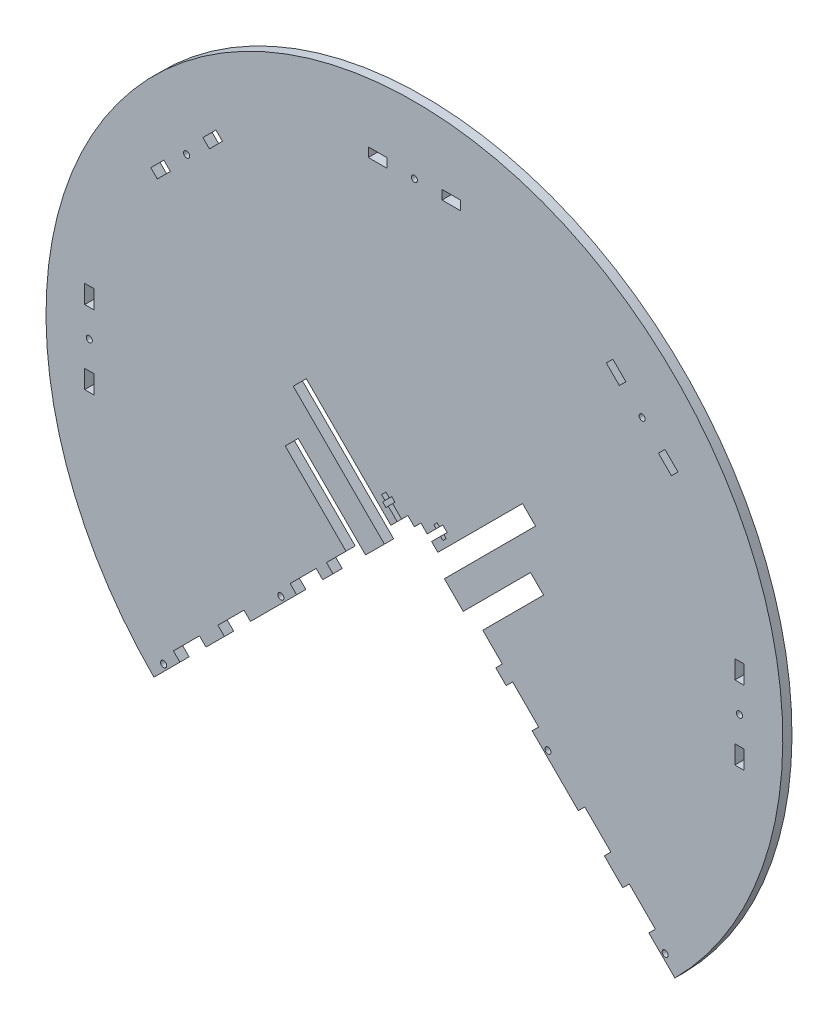
SolidWorks part; units mm, degrees
ref_plane "Front Plane" through (0, 0, 0) normal (0, 0, 1) x (1, 0, 0)
ref_plane "Top Plane" through (0, 0, 0) normal (0, 1, 0) x (1, 0, 0)
ref_plane "Right Plane" through (0, 0, 0) normal (1, 0, 0) x (0, 0, -1)
sketch "Sketch1" plane through (0, 0, 0) normal (0, 0, 1) x (1, 0, 0)
  circle A0 centre (0, -210.9923) radius 254
  arc A1 (184.0391, -386.0511) -> (248.1989, -264.9673) centre (0, -210.9923) ccw construction
extrude "Boss-Extrude1" add sketch "Sketch1" along normal blind 6.35 contours A0
sketch "Sketch3" plane through (0, 0, 0) normal (0, 0, -1) x (-1, 0, 0)
  line L0 (179.6051, -390.5974) -> (0, -210.9923)
  line L1 (0, -210.9923) -> (-179.6051, -390.5974)
  line L2 (91.3112, -302.3035) -> (113.0075, -323.9998) construction
  line L3 (-179.6051, -390.5974) -> (-172.1335, -383.1258) construction
  circle A0 centre (0, -210.9923) radius 254 construction
  arc A1 (179.6051, -390.5974) -> (-179.6051, -390.5974) centre (0, -210.9923) cw
extrude "Cut-Extrude1" cut sketch "Sketch3" against normal through all
sketch "Sketch4" plane through (0, 0, 6.35) normal (0, 0, 1) x (1, 0, 0)
  line L0 (-161.6446, -372.6369) -> (-166.1347, -368.1468)
  line L1 (-161.6446, -372.6369) -> (-143.6841, -354.6764)
  line L2 (-166.1347, -368.1468) -> (-148.1742, -350.1862)
  line L3 (-143.6841, -354.6764) -> (-148.1742, -350.1862)
  line L4 (-179.6051, -390.5974) -> (0, -210.9923) construction
  line L5 (-166.1347, -368.1468) -> (-161.6446, -372.6369) construction
  line L7 (-130.9681, -341.9603) -> (-135.4582, -337.4702)
  line L8 (-130.9681, -341.9603) -> (-113.0075, -323.9998)
  line L9 (-135.4582, -337.4702) -> (-117.4977, -319.5097)
  line L10 (-113.0075, -323.9998) -> (-117.4977, -319.5097)
  line L11 (-81.1905, -292.1828) -> (-85.6806, -287.6926)
  line L12 (-81.1905, -292.1828) -> (-63.23, -274.2223)
  line L13 (-85.6806, -287.6926) -> (-67.7201, -269.7321)
  line L14 (-63.23, -274.2223) -> (-67.7201, -269.7321)
  line L15 (-85.6806, -287.6926) -> (-81.1905, -292.1828) construction
  line L17 (-56.1266, -267.1189) -> (-60.6167, -262.6287)
  line L18 (-56.1266, -267.1189) -> (-33.676, -244.6682)
  line L19 (-60.6167, -262.6287) -> (-38.1661, -240.1781)
  line L20 (-33.676, -244.6682) -> (-38.1661, -240.1781)
  line L21 (-11.6893, -222.6816) -> (-16.1795, -218.1915)
  line L22 (-11.6893, -222.6816) -> (0, -210.9923)
  line L23 (-16.1795, -218.1915) -> (-4.4901, -206.5021)
  line L24 (0, -210.9923) -> (-4.4901, -206.5021)
  line L25 (-16.1795, -218.1915) -> (-11.6893, -222.6816) construction
  line L27 (-143.6841, -354.6764) -> (-148.1742, -350.1862) construction
  line L28 (-135.4582, -337.4702) -> (-130.9681, -341.9603) construction
  line L29 (-113.0075, -323.9998) -> (-117.4977, -319.5097) construction
  line L30 (-63.23, -274.2223) -> (-67.7201, -269.7321) construction
  line L31 (0, -210.9923) -> (-4.4901, -206.5021) construction
  line L32 (-60.6167, -262.6287) -> (-38.1661, -240.1781) construction
  line L33 (-60.6167, -262.6287) -> (-56.1266, -267.1189) construction
  line L34 (-38.1661, -240.1781) -> (-33.676, -244.6682) construction
extrude "Cut-Extrude2" cut sketch "Sketch4" against normal through all
mirror "Mirror1" about plane through (0, 0, 0) normal (1, 0, 0) of "Cut-Extrude2"
sketch "Sketch5" plane through (0, 0, 6.35) normal (0, 0, 1) x (1, 0, 0)
  line L0 (177.245, -91.8888) -> (181.7351, -87.3987)
  line L1 (-31.75, 0) -> (-19.05, 0)
  line L2 (-31.75, 0) -> (-31.75, -6.35)
  line L3 (-31.75, -6.35) -> (-19.05, -6.35)
  line L4 (-19.05, 0) -> (-19.05, -6.35)
  line L5 (19.05, 0) -> (31.75, 0)
  line L6 (19.05, 0) -> (19.05, -6.35)
  line L7 (19.05, -6.35) -> (31.75, -6.35)
  line L8 (31.75, 0) -> (31.75, -6.35)
  line L9 (-227.33, -242.7423) -> (-220.98, -242.7423)
  line L10 (-227.33, -242.7423) -> (-227.33, -230.0423)
  line L11 (-227.33, -230.0423) -> (-220.98, -230.0423)
  line L12 (-220.98, -242.7423) -> (-220.98, -230.0423)
  line L13 (-227.33, -179.2423) -> (-220.98, -179.2423)
  line L14 (-227.33, -179.2423) -> (-227.33, -191.9423)
  line L15 (-227.33, -191.9423) -> (-220.98, -191.9423)
  line L16 (-220.98, -179.2423) -> (-220.98, -191.9423)
  line L17 (220.98, -179.2423) -> (227.33, -179.2423)
  line L18 (220.98, -179.2423) -> (220.98, -191.9423)
  line L19 (220.98, -191.9423) -> (227.33, -191.9423)
  line L20 (227.33, -179.2423) -> (227.33, -191.9423)
  line L21 (220.98, -230.0423) -> (227.33, -230.0423)
  line L22 (220.98, -230.0423) -> (220.98, -242.7423)
  line L23 (220.98, -242.7423) -> (227.33, -242.7423)
  line L24 (227.33, -230.0423) -> (227.33, -242.7423)
  line L25 (177.245, -91.8888) -> (168.2647, -82.9085)
  line L26 (181.7351, -87.3987) -> (172.7548, -78.4184)
  line L27 (168.2647, -82.9085) -> (172.7548, -78.4184)
  line L28 (172.7548, -78.4184) -> (168.2647, -82.9085) construction
  line L29 (141.3239, -55.9678) -> (145.8141, -51.4776)
  line L30 (141.3239, -55.9678) -> (132.3437, -46.9875)
  line L31 (145.8141, -51.4776) -> (136.8338, -42.4974)
  line L32 (132.3437, -46.9875) -> (136.8338, -42.4974)
  line L33 (136.8338, -42.4974) -> (132.3437, -46.9875) construction
  line L34 (-177.245, -91.8888) -> (-181.7351, -87.3987)
  line L35 (-177.245, -91.8888) -> (-168.2647, -82.9085)
  line L36 (-181.7351, -87.3987) -> (-172.7548, -78.4184)
  line L37 (-168.2647, -82.9085) -> (-172.7548, -78.4184)
  line L38 (-168.2647, -82.9085) -> (-172.7548, -78.4184) construction
  line L39 (-141.3239, -55.9678) -> (-145.8141, -51.4776)
  line L40 (-141.3239, -55.9678) -> (-132.3437, -46.9875)
  line L41 (-145.8141, -51.4776) -> (-136.8338, -42.4974)
  line L42 (-132.3437, -46.9875) -> (-136.8338, -42.4974)
  line L43 (-132.3437, -46.9875) -> (-136.8338, -42.4974) construction
extrude "Cut-Extrude3" cut sketch "Sketch5" against normal through all
sketch "Sketch6" plane through (0, 0, 6.35) normal (0, 0, 1) x (1, 0, 0)
  line L0 (-189.391, -362.851) -> (-147.7076, -404.5344) construction
  line L1 (-176.6237, -378.6357) -> (-172.1335, -383.1258) construction
  line L2 (-173.6063, -375.6183) -> (-169.1162, -380.1085) construction
  line L3 (-136.5306, -343.0327) -> (-168.0044, -374.5065) construction
  line L4 (-148.1742, -350.1862) -> (-166.1347, -368.1468) construction
  line L5 (-143.6841, -354.6764) -> (-130.9681, -341.9603) construction
  line L6 (-119.5963, -271.0011) -> (-74.6896, -315.9078) construction
  line L7 (-95.8014, -297.8134) -> (-91.3112, -302.3035) construction
  line L8 (-92.784, -294.796) -> (-88.2939, -299.2862) construction
  circle A0 centre (-172.8699, -379.3721) radius 2.0955
  circle A1 centre (-92.0476, -298.5498) radius 2.0955
  dimension "D1" = 4.191
extrude "Cut-Extrude4" cut sketch "Sketch6" against normal through all
mirror "Mirror2" about plane through (0, 0, 0) normal (1, 0, 0) of "Cut-Extrude4"
sketch "Sketch7" plane through (0, 0, 6.35) normal (0, 0, 1) x (1, 0, 0)
  line L0 (170.4831, -53.7494) -> (119.6731, -104.5593) construction
  line L1 (239.3418, -210.9923) -> (189.3468, -210.9923) construction
  line L2 (0, 19.4565) -> (0, -42.3568) construction
  line L3 (-175.6943, -48.5381) -> (-146.0554, -78.1771) construction
  line L4 (-242.378, -210.9923) -> (-203.5636, -210.9923) construction
  line L5 (-2.1336, -6.35) -> (-2.1336, 0) construction
  line L6 (2.1336, -6.35) -> (2.1336, 0) construction
  line L7 (160.7931, -66.4567) -> (156.303, -70.9468) construction
  line L8 (157.7758, -63.4393) -> (153.2856, -67.9295) construction
  line L9 (220.98, -208.8714) -> (227.33, -208.8714) construction
  line L10 (220.98, -213.1132) -> (227.33, -213.1132) construction
  line L11 (-156.303, -70.9468) -> (-160.7931, -66.4567) construction
  line L12 (-153.2856, -67.9295) -> (-157.7758, -63.4393) construction
  line L13 (-227.33, -213.1132) -> (-220.98, -213.1132) construction
  line L14 (-227.33, -208.8714) -> (-220.98, -208.8714) construction
  line L15 (-224.155, -150.312) -> (-224.155, -266.4456) construction
  line L16 (-118.4045, -28.5582) -> (-198.2831, -108.4368) construction
  line L17 (-31.3546, -3.175) -> (26.462, -3.175) construction
  line L18 (131.6344, -41.7881) -> (173.4787, -83.6324) construction
  line L19 (224.155, -139.5418) -> (224.155, -241.3145) construction
  line L20 (220.98, -179.2423) -> (220.98, -191.9423) construction
  line L21 (227.33, -191.9423) -> (227.33, -179.2423) construction
  line L22 (141.3239, -55.9678) -> (132.3437, -46.9875) construction
  line L23 (145.8141, -51.4776) -> (136.8338, -42.4974) construction
  line L24 (-19.05, 0) -> (-31.75, 0) construction
  line L25 (-31.75, -6.35) -> (-19.05, -6.35) construction
  line L26 (-172.7548, -78.4184) -> (-181.7351, -87.3987) construction
  line L27 (-177.245, -91.8888) -> (-168.2647, -82.9085) construction
  line L28 (-227.33, -179.2423) -> (-227.33, -191.9423) construction
  line L29 (-220.98, -191.9423) -> (-220.98, -179.2423) construction
  circle A0 centre (-224.155, -210.9923) radius 2.0955
  circle A1 centre (-157.0394, -67.1931) radius 2.0955
  circle A2 centre (0, -3.175) radius 2.0955
  circle A3 centre (157.0394, -67.1931) radius 2.0955
  circle A4 centre (224.155, -210.9923) radius 2.0955
  dimension "D1" = 4.191
extrude "Cut-Extrude5" cut sketch "Sketch7" against normal through all
sketch "Sketch8" plane through (0, 0, 6.35) normal (0, 0, 1) x (1, 0, 0)
  line L0 (-20.6696, -231.6619) -> (-11.6893, -222.6816)
  line L1 (-20.6696, -231.6619) -> (-83.5314, -168.8001)
  line L2 (-11.6893, -222.6816) -> (-74.5511, -159.8198)
  line L3 (-83.5314, -168.8001) -> (-74.5511, -159.8198)
  line L4 (-33.676, -244.6682) -> (-11.6893, -222.6816) construction
  line L5 (-8.7612, -234.5899) -> (-94.7474, -148.6038) construction
  line L6 (-77.7195, -170.1218) -> (-52.225, -195.6163) construction
  line L7 (-73.2293, -165.6317) -> (-47.7349, -191.1262) construction
  line L8 (-16.1795, -218.1915) -> (-11.6893, -222.6816) construction
  dimension "D1" = 88.9
extrude "Cut-Extrude6" cut sketch "Sketch8" against normal through all
mirror "Mirror3" about plane through (0, 0, 0) normal (1, 0, 0) of "Cut-Extrude6"
sketch "Sketch9" plane through (0, 0, 6.35) normal (0, 0, 1) x (1, 0, 0)
  line L0 (-28.1989, -194.4827) -> (-15.046, -207.6356) construction
  line L1 (-4.4901, -206.5021) -> (0, -210.9923) construction
  line L2 (-16.1795, -218.1915) -> (-11.6893, -222.6816) construction
  line L3 (-4.4901, -206.5021) -> (-16.1795, -218.1915) construction
  line B0 (-11.8435, -213.8555) -> (-8.8261, -210.8381)
  line B1 (-17.2675, -202.3967) -> (-15.6331, -200.7623)
  line B2 (-15.6331, -200.7623) -> (-13.3881, -203.0073)
  line B3 (-13.3881, -203.0073) -> (-15.0225, -204.6417)
  line B4 (-15.0225, -204.6417) -> (-8.8261, -210.8381)
  line B5 (-17.2675, -202.3967) -> (-19.6024, -200.0618)
  line B6 (-19.6024, -200.0618) -> (-22.6198, -203.0792)
  line B7 (-20.2849, -205.4141) -> (-22.6198, -203.0792)
  line B8 (-18.0398, -207.6591) -> (-11.8435, -213.8555)
  line B9 (-19.6743, -209.2935) -> (-18.0398, -207.6591)
  line B10 (-21.9193, -207.0485) -> (-19.6743, -209.2935)
  line B11 (-20.2849, -205.4141) -> (-21.9193, -207.0485)
sketch_block_instance "TSlot-1"
sketch_block "TSlot" parameters "D1"=3.302, "D2"=3.175
extrude "Cut-Extrude7" cut sketch "Sketch9" against normal through all
mirror "Mirror4" about plane through (0, 0, 0) normal (1, 0, 0) of "Cut-Extrude7"
sketch "Sketch10" plane through (0, 0, 6.35) normal (0, 0, 1) x (1, 0, 0)
  line L0 (-92.7156, -190.1188) -> (-17.7162, -265.1181) construction
  line L1 (-80.0807, -207.2437) -> (-42.6562, -244.6682) construction
  line L2 (-38.1661, -240.1781) -> (-75.5906, -202.7536) construction
  line L3 (-80.0807, -198.2635) -> (-89.061, -207.2437)
  line L4 (-80.0807, -198.2635) -> (-33.676, -244.6682)
  line L5 (-89.061, -207.2437) -> (-42.6562, -253.6485)
  line L6 (-33.676, -244.6682) -> (-42.6562, -253.6485)
  line L7 (-33.676, -244.6682) -> (-20.6696, -231.6619) construction
  line L8 (-75.5906, -202.7536) -> (-80.0807, -207.2437) construction
  dimension "D1" = 6.35
  dimension "D2" = 6.35
extrude "Cut-Extrude8" cut sketch "Sketch10" against normal through all
mirror "Mirror5" about plane through (0, 0, 0) normal (1, 0, 0) of "Cut-Extrude8"
